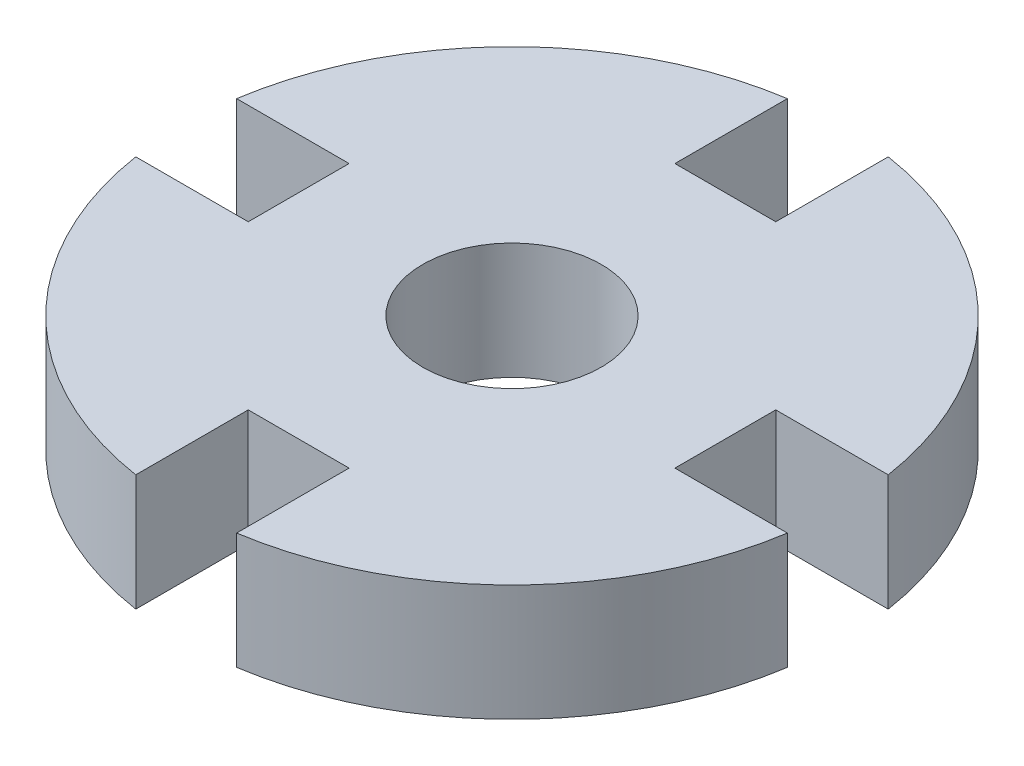
SolidWorks part; units mm, degrees
ref_plane "Front Plane" through (0, 0, 0) normal (0, 0, 1) x (1, 0, 0)
ref_plane "Top Plane" through (0, 0, 0) normal (0, 1, 0) x (1, 0, 0)
ref_plane "Right Plane" through (0, 0, 0) normal (1, 0, 0) x (0, 0, -1)
sketch "Sketch1" plane through (0, 0, 0) normal (0, 1, 0) x (1, 0, 0)
  circle A0 centre (0, 0) radius 8.5
  circle A1 centre (0, 0) radius 2.3
  circle A2 centre (0, 0) radius 2.3 construction
  point P8 (0, -8.5)
  dimension "D1" = 3
extrude "Boss-Extrude1" add sketch "Sketch1" along normal blind 1.5 and the other way blind 1.5
sketch "Sketch2" plane through (0, 1.5, 0) normal (0, 1, 0) x (1, 0, 0)
  line L0 (-8.5, 1.3) -> (-5.5, 1.3)
  line L1 (1.3, -8.5) -> (-1.3, -8.5)
  line L2 (1.3, -8.5) -> (1.3, -5.5)
  line L3 (1.3, -5.5) -> (-1.3, -5.5)
  line L4 (-1.3, -8.5) -> (-1.3, -5.5)
  line L5 (0, -5.5) -> (0, -8.5) construction
  line L6 (1.3, -7) -> (-1.3, -7) construction
  line L7 (-5.5, -1.3) -> (-5.5, 1.3)
  line L8 (-8.5, -1.3) -> (-5.5, -1.3)
  line L9 (-8.5, -1.3) -> (-8.5, 1.3)
  line L10 (1.3, 8.5) -> (1.3, 5.5)
  line L11 (-1.3, 5.5) -> (1.3, 5.5)
  line L12 (-1.3, 8.5) -> (-1.3, 5.5)
  line L13 (-1.3, 8.5) -> (1.3, 8.5)
  line L14 (8.5, -1.3) -> (5.5, -1.3)
  line L15 (5.5, 1.3) -> (5.5, -1.3)
  line L16 (8.5, 1.3) -> (5.5, 1.3)
  line L17 (8.5, 1.3) -> (8.5, -1.3)
  circle A0 centre (0, 0) radius 8.5 construction
  point P0 (0, -7)
  point P21 (0, 0)
  dimension "D1" = 0
  dimension "D2" = 2.6
  dimension "D3" = 4
extrude "Cut-Extrude1" cut sketch "Sketch2" against normal through all
